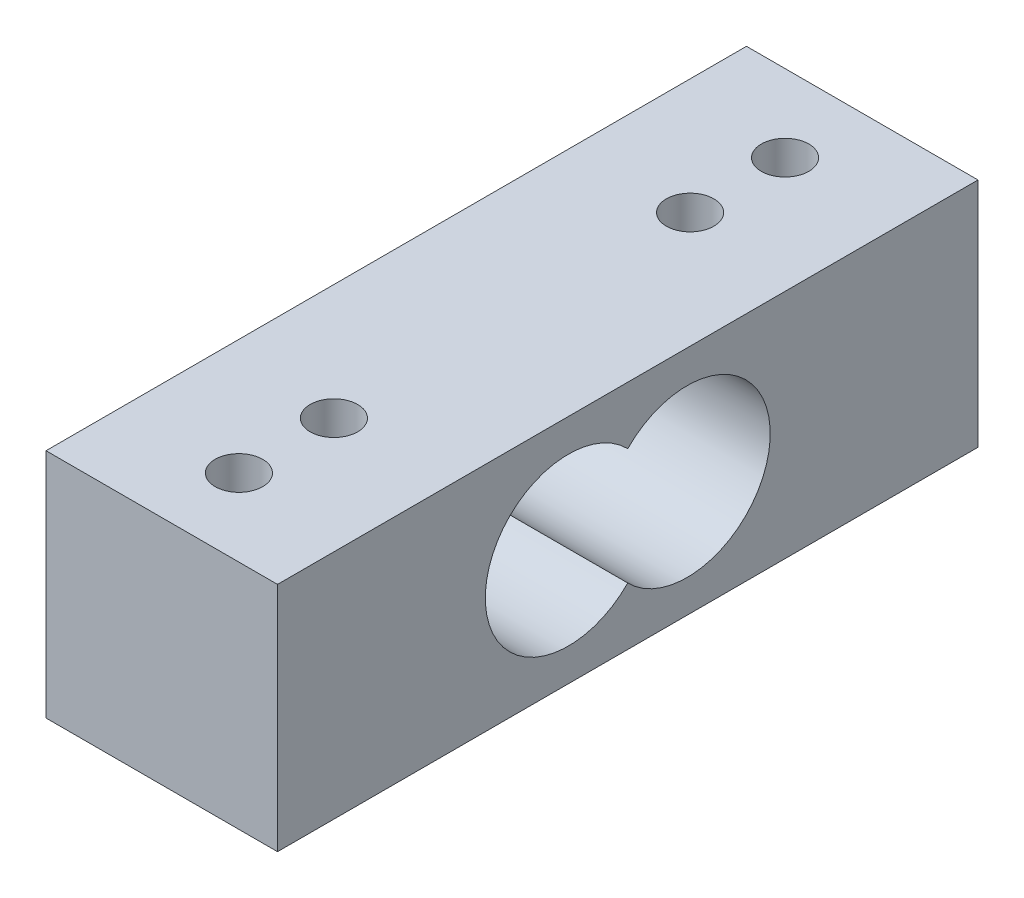
SolidWorks part; units mm, degrees
ref_plane "Plan de face" through (0, 0, 0) normal (0, 0, 1) x (1, 0, 0)
ref_plane "Plan de dessus" through (0, 0, 0) normal (0, 1, 0) x (1, 0, 0)
ref_plane "Plan de droite" through (0, 0, 0) normal (1, 0, 0) x (0, 0, -1)
sketch "Esquisse1" plane through (0, 0, 0) normal (0, 0, 1) x (1, 0, 0)
  line L0 (0, 19.2175) -> (0, -29.9729) construction
  line L1 (-9.75, 9.75) -> (9.75, 9.75)
  line L2 (-9.75, 9.75) -> (-9.75, -9.75)
  line L3 (-9.75, -9.75) -> (9.75, -9.75)
  line L4 (9.75, 9.75) -> (9.75, -9.75)
  line L5 (-22.701, 0) -> (33.2907, 0) construction
  dimension "D1" = 19.5
extrude "Boss.-Extru.1" add sketch "Esquisse1" against normal mid plane 59
sketch "Esquisse2" plane through (0, 9.75, 0) normal (0, 1, 0) x (1, 0, 0)
  line L0 (0, 29.5) -> (0, -29.5) construction
  line L1 (9.75, 29.5) -> (-9.75, 29.5) construction
  line L2 (9.75, -29.5) -> (-9.75, -29.5) construction
  line L3 (-9.75, 0) -> (9.75, 0) construction
  line L4 (-9.75, 29.5) -> (-9.75, -29.5) construction
  line L5 (9.75, 29.5) -> (9.75, -29.5) construction
  circle A0 centre (0, 23) radius 2
  circle A1 centre (0, 15) radius 2
  circle A2 centre (0, -15) radius 2
  circle A3 centre (0, -23) radius 2
  dimension "D3" = 4
  dimension "D1" = 8
  dimension "D2" = 30
extrude "Enlèv. mat.-Extru.1" cut sketch "Esquisse2" against normal through all
sketch "Esquisse3" plane through (9.75, 0, 0) normal (1, 0, 0) x (0, 0, -1)
  line L0 (-29.5, 0) -> (29.5, 0) construction
  line L1 (-29.5, -9.75) -> (-29.5, 9.75) construction
  line L2 (29.5, -9.75) -> (29.5, 9.75) construction
  line L3 (0, 9.75) -> (0, -9.75) construction
  line L4 (29.5, 9.75) -> (-29.5, 9.75) construction
  line L5 (29.5, -9.75) -> (-29.5, -9.75) construction
  arc A0 (0, 4.899) -> (0, -4.899) centre (-5, 0) ccw
  arc A1 (0, -4.899) -> (0, 4.899) centre (5, 0) ccw
  dimension "D2" = 14
  dimension "D1" = 10
extrude "Enlèv. mat.-Extru.2" cut sketch "Esquisse3" against normal through all
ref_axis "Axe1" through (0, 0, -32.45) along (0, 0, 1)
ref_axis "Axe2" through (10.725, 0, 0) along (-1, 0, 0)
ref_plane "Plan1" through (0, 0, 23) normal (0, 0, -1) x (-1, 0, 0)
ref_plane "Plan2" through (0, 0, 15) normal (0, 0, -1) x (-1, 0, 0)
ref_plane "Plan3" through (0, 0, 19) normal (0, 0, -1) x (-1, 0, 0)
ref_axis "Axe3" through (0, -27.7396, 19) along (0, 1, 0)
ref_plane "Plan4" through (0, 0, -15) normal (0, 0, -1) x (-1, 0, 0)
ref_plane "Plan5" through (0, 0, -23) normal (0, 0, -1) x (-1, 0, 0)
ref_plane "Plan6" through (0, 0, -19) normal (0, 0, -1) x (-1, 0, 0)
ref_axis "Axe4" through (0, 50.0677, -19) along (0, -1, 0)
